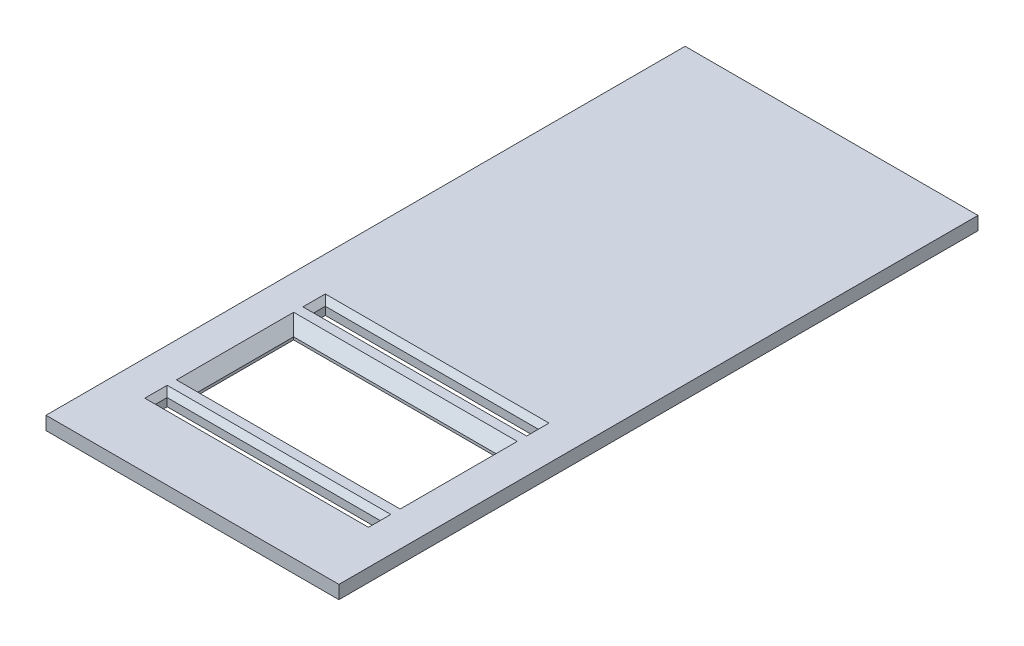
SolidWorks part; units mm, degrees
ref_plane "Front Plane" through (0, 0, 0) normal (0, 0, 1) x (1, 0, 0)
ref_plane "Top Plane" through (0, 0, 0) normal (0, 1, 0) x (1, 0, 0)
ref_plane "Right Plane" through (0, 0, 0) normal (1, 0, 0) x (0, 0, -1)
sketch "Sketch1" plane through (0, 0, 0) normal (0, 1, 0) x (1, 0, 0)
  line L1 (-69.85, -50.8) -> (69.85, -50.8)
  line L2 (-69.85, -50.8) -> (-69.85, 254)
  line L3 (-69.85, 254) -> (69.85, 254)
  line L4 (69.85, -50.8) -> (69.85, 254)
  line L5 (0, 254) -> (0, -50.8) construction
  line L6 (-69.85, 101.6) -> (69.85, 101.6) construction
  point P0 (0, 101.6)
  dimension "D1" = 304.8
  dimension "D2" = 139.7
  dimension "D3" = 101.6
extrude "Boss-Extrude1" add sketch "Sketch1" along normal blind 6.35
sketch "Sketch2" plane through (0, 6.35, 0) normal (0, 1, 0) x (1, 0, 0)
  line L0 (-69.85, -50.8) -> (69.85, -50.8) construction
  line L1 (-48.26, 0) -> (48.26, 0)
  line L2 (-48.26, 0) -> (-48.26, 45.72)
  line L3 (-48.26, 45.72) -> (48.26, 45.72)
  line L4 (48.26, 0) -> (48.26, 45.72)
  line L5 (0, 45.72) -> (0, 0) construction
  line L6 (-48.26, 22.86) -> (48.26, 22.86) construction
  point P0 (0, 22.86)
  dimension "D1" = 45.72
  dimension "D2" = 96.52
  dimension "D3" = 50.8
extrude "Main Hole" cut sketch "Sketch2" against normal through all
ref_plane "Plane1" through (0, 0, -22.86) normal (0, 0, 1) x (1, 0, 0)
sketch "Sketch3" plane through (0, 6.35, 0) normal (0, 1, 0) x (1, 0, 0)
  line L0 (48.26, 45.72) -> (-48.26, 45.72) construction
  line L1 (-50.8, 57.785) -> (50.8, 57.785)
  line L2 (-50.8, 57.785) -> (-50.8, 63.373)
  line L3 (-50.8, 63.373) -> (50.8, 63.373)
  line L4 (50.8, 57.785) -> (50.8, 63.373)
  point P4 (0, 57.785)
  dimension "D1" = 101.6
  dimension "D2" = 5.588
  dimension "D3" = 12.065
extrude "NeoPixel" cut sketch "Sketch3" against normal through all
mirror "Mirror2" about plane through (0, 0, -22.86) normal (0, 0, 1) of "NeoPixel"
sketch "Sketch5" plane through (0, 0, 0) normal (0, -1, 0) x (1, 0, 0)
  line L0 (69.85, -254) -> (-69.85, -254) construction
  line L1 (67.31, -251.46) -> (-67.31, -251.46)
  line L2 (67.31, -251.46) -> (67.31, 48.26)
  line L3 (67.31, 48.26) -> (-67.31, 48.26)
  line L4 (-67.31, -251.46) -> (-67.31, 48.26)
  line L5 (64.77, -248.92) -> (-64.77, -248.92)
  line L6 (64.77, -248.92) -> (64.77, 45.72)
  line L7 (64.77, 45.72) -> (-64.77, 45.72)
  line L8 (-64.77, -248.92) -> (-64.77, 45.72)
  line L9 (-69.85, -254) -> (-69.85, 50.8) construction
  line L10 (-69.85, 50.8) -> (69.85, 50.8) construction
  line L11 (69.85, 50.8) -> (69.85, -254) construction
  dimension "D1" = 2.54
  dimension "D2" = 2.54
  dimension "D3" = 2.54
  dimension "D4" = 2.54
  dimension "D5" = 2.54
  dimension "D6" = 2.54
  dimension "D7" = 2.54
  dimension "D8" = 2.54
extrude "Boss-Extrude2" add sketch "Sketch5" along normal blind 2.54 contours L4 L1 L2 L3 L5 L8 L7 L6 region at (0, 0, -251.1314)
chamfer "Chamfer1" distance 2.54 angle 45 8 edges at (50.8, 6.35, 14.859) (0, 6.35, 17.653) (-50.8, 6.35, 14.859) (0, 6.35, 12.065) (-50.8, 6.35, -60.579) (0, 6.35, -57.785) (50.8, 6.35, -60.579) (0, 6.35, -63.373)
chamfer "Chamfer2" distance 5.08 angle 45 4 edges at (48.26, 6.35, -22.86) (0, 6.35, 0) (-48.26, 6.35, -22.86) (0, 6.35, -45.72)
sketch "Sketch6" plane through (0, 0, 0) normal (0, -1, 0) x (1, 0, 0)
  line L0 (0.6985, -22.86) -> (-0.6985, -22.86) construction
  line L1 (50.8, 2.54) -> (-50.8, 2.54)
  line L2 (50.8, 2.54) -> (50.8, -48.26)
  line L3 (50.8, -48.26) -> (-50.8, -48.26)
  line L4 (-50.8, 2.54) -> (-50.8, -48.26)
  line L5 (0, -48.26) -> (0, 2.54) construction
  line L6 (50.8, -22.86) -> (-50.8, -22.86) construction
  line L7 (0, -4.8895) -> (0, 4.8895) construction
  line L8 (6.35, -50.8) -> (6.35, -48.26)
  line L9 (53.34, 5.08) -> (-53.34, 5.08)
  line L10 (53.34, 5.08) -> (53.34, -50.8)
  line L11 (53.34, -50.8) -> (-53.34, -50.8)
  line L12 (-53.34, 5.08) -> (-53.34, -50.8)
  line L13 (0, -50.8) -> (0, 5.08) construction
  line L14 (53.34, -22.86) -> (-53.34, -22.86) construction
  line L31 (-6.35, -50.8) -> (-6.35, -48.26)
  line L32 (6.35, -49.53) -> (-6.35, -49.53) construction
  point P0 (0, -22.86)
  point P8 (0, -22.86)
  point P16 (0, -49.53)
  dimension "D1" = 2.54
  dimension "D2" = 2.54
  dimension "D3" = 50.8
  dimension "D4" = 101.6
  dimension "D5" = 12.7
extrude "Boss-Extrude3" [suppressed] add sketch "Sketch6" along normal blind 4.064 contours L9 L12 L11 L10 L4 L1 L2 L3
equation "\"D1@Sketch2\"=1.8in"
equation "\"D2@Sketch2\"=3.8in"
